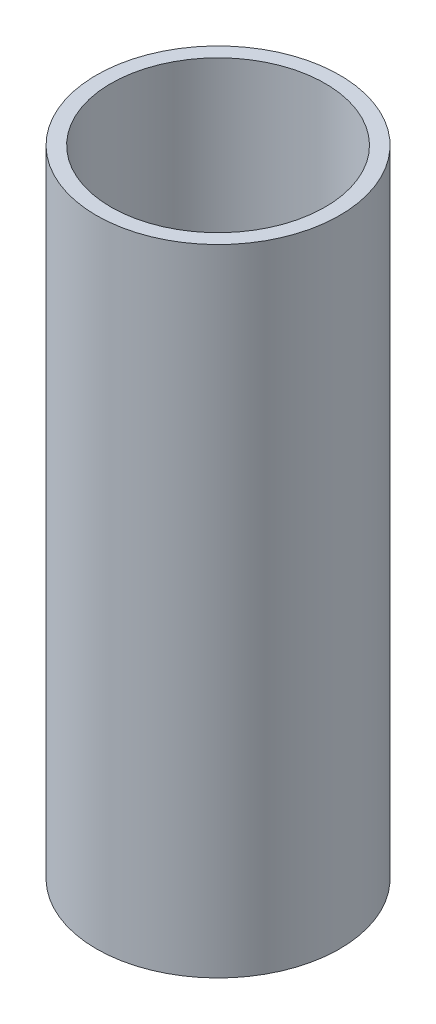
SolidWorks part; units mm, degrees
ref_plane "Front Plane" through (0, 0, 0) normal (0, 0, 1) x (1, 0, 0)
ref_plane "Top Plane" through (0, 0, 0) normal (0, 1, 0) x (1, 0, 0)
ref_plane "Right Plane" through (0, 0, 0) normal (1, 0, 0) x (0, 0, -1)
sketch "Sketch1" plane through (0, 0, 0) normal (0, 1, 0) x (1, 0, 0)
  circle A0 centre (0, 0) radius 57.5
  dimension "SLEEVE_OD" = 115
extrude "Boss-Extrude1" add sketch "Sketch1" along normal blind 300.2415
sketch "Sketch2" plane through (0, 0, 0) normal (0, 1, 0) x (1, 0, 0)
  circle A0 centre (0, 0) radius 50.6301
  dimension "BORE_D" = 101.2602
extrude "Cut-Extrude1" cut sketch "Sketch2" along normal through all
chamfer "Chamfer1" distance 2.3828 angle 66.091 rebuild error yes
